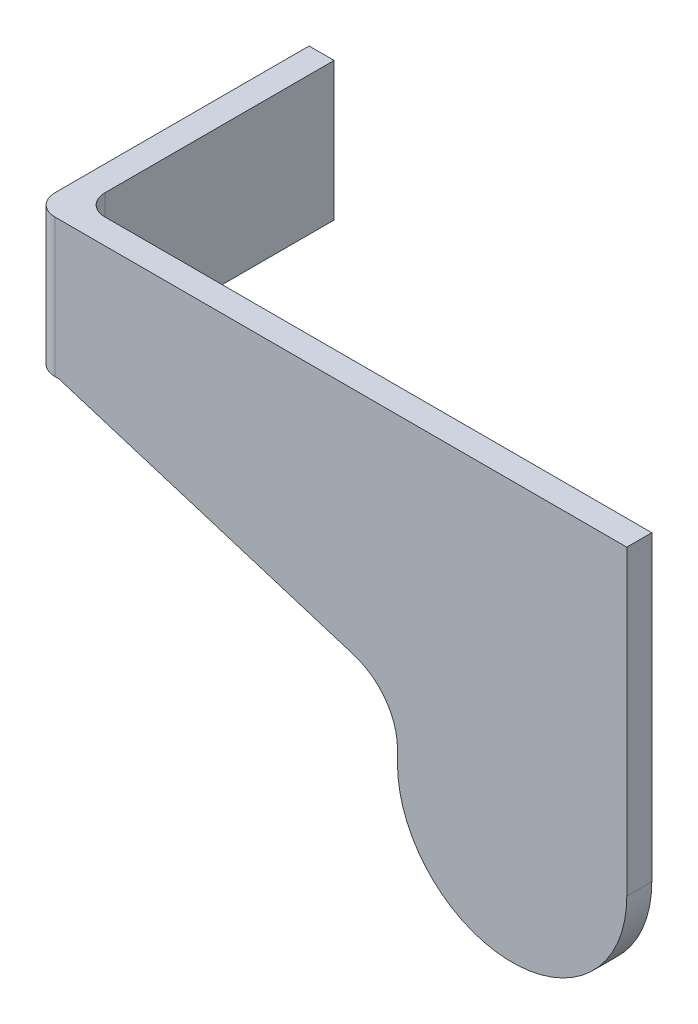
SolidWorks part; units mm, degrees
ref_plane "Piano frontale" through (0, 0, 0) normal (0, 0, 1) x (1, 0, 0)
ref_plane "Piano superiore" through (0, 0, 0) normal (0, 1, 0) x (1, 0, 0)
ref_plane "Piano destro" through (0, 0, 0) normal (1, 0, 0) x (0, 0, -1)
sketch "Schizzo2" plane through (0, 0, 0) normal (0, 0, 1) x (1, 0, 0)
  line L0 (0, 0) -> (0, 45) construction
  line L1 (-27.5, 0) -> (-27.5, 45)
  line L2 (27.5, 0) -> (27.5, 45)
  arc A0 (-27.5, 0) -> (27.5, 0) centre (0, 0) ccw
  arc A1 (27.5, 45) -> (-27.5, 45) centre (0, 45) ccw
  point P3 (0, 22.5)
  point P8 (0, -27.5)
  point P9 (0, 72.5)
  dimension "D1" = 100
  dimension "D2" = 55
extrude "Estrusione-Estrusione1" add sketch "Schizzo2" along normal blind 6
sketch "Schizzo3" plane through (0, 0, 0) normal (0, 0, 1) x (1, 0, 0)
  line L1 (27.5, 0) -> (-108.7, 0)
  line L2 (27.5, 0) -> (27.5, 72.5)
  line L3 (27.5, 72.5) -> (-108.7, 72.5)
  line L4 (-108.7, 0) -> (-108.7, 72.5)
  arc A0 (27.5, 45) -> (-27.5, 45) centre (0, 45) ccw construction
  point P5 (0, 0)
  point P9 (0, 72.5)
  dimension "D1" = 136.2
  dimension "D2" = 72.5
  dimension "D3" = 72.5
extrude "Estrusione-Estrusione2" add sketch "Schizzo3" along normal blind 6
sketch "Schizzo4" plane through (0, 0, 6) normal (0, 0, 1) x (1, 0, 0)
  line L2 (-27.5, 0) -> (-108.7, 0)
  line L3 (-108.7, 0) -> (-108.7, 39.3472)
  line L4 (-108.7, 39.3472) -> (-27.5, 14.1424)
  line L5 (-27.5, 14.1424) -> (-27.5, 0)
  line L6 (-108.7, 72.5) -> (-108.7, 0) construction
  point P2 (0, 0)
  point P3 (-108.7, 39.3472)
  point P5 (-108.7, 68.75)
  point P8 (-108.7, 68.75)
extrude "Taglio-Estrusione1" cut sketch "Schizzo4" against normal through all
fillet "Raccordo5" radius 15 1 edges at (-27.5, 14.1424, 3) type face fillet first side face at (-68.1, 26.7448, 3) second side face at (0, -13.75, 3) second side face at (-27.5, 7.0712, 3)
sketch "Schizzo9" plane through (0, 0, 0) normal (0, 0, 1) x (1, 0, 0)
  line L0 (-108.7, 39.3472) -> (-114.7, 39.3472)
  line L1 (-114.7, 39.3472) -> (-114.7, 72.5)
  line L2 (-114.7, 72.5) -> (-108.7, 72.5)
  line L3 (-108.7, 72.5) -> (-108.7, 39.3472)
extrude "Estrusione-Estrusione5" add sketch "Schizzo9" against normal blind 60 and the other way up to vertex (6 mm away) other way up to point (-108.7, 72.5, 6)
sketch "Schizzo10" plane through (0, 0, 6) normal (0, 0, 1) x (1, 0, 0)
  line L1 (-114.7, 55.9236) -> (39.3153, 55.9236)
  line L2 (-114.7, 72.5) -> (-114.7, 39.3472) construction
  dimension "D1" = 55.9236
fillet "Raccordo6" radius 5 1 edges at (-108.7, 55.9236, 0) type face fillet first side face at (-36.1571, 25.5845, 0) second side face at (-108.7, 55.9236, -30)
fillet "Raccordo7" radius 5 1 edges at (-114.7, 55.9236, 6)
